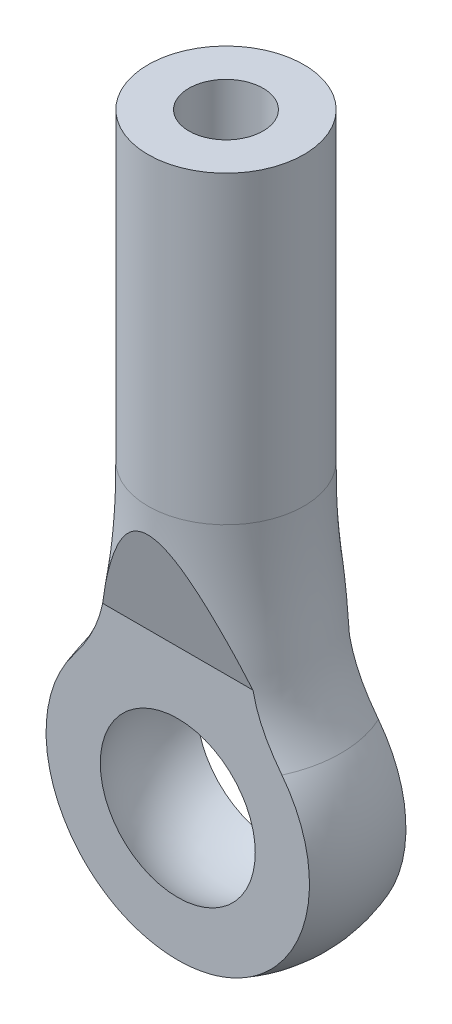
SolidWorks part; units mm, degrees
ref_plane "Front Plane" through (0, 0, 0) normal (0, 0, 1) x (1, 0, 0)
ref_plane "Top Plane" through (0, 0, 0) normal (0, 1, 0) x (1, 0, 0)
ref_plane "Right Plane" through (0, 0, 0) normal (1, 0, 0) x (0, 0, -1)
sketch "Sketch1" plane through (0, 0, 0) normal (0, 0, 1) x (1, 0, 0)
  line L0 (0, 15.65) -> (0, 0) construction
  line L1 (0, 15.65) -> (-2.1, 15.65)
  line L2 (-2.1, 15.65) -> (-2.1, 7.4436)
  line L3 (-2.1, 4.7666) -> (-2.1, 5.7762) construction
  line L4 (-3.3145, 1.8573) -> (-2.8734, 2.4859) construction
  line L5 (-5.6007, -3.78) -> (7.1758, -3.78) construction
  line L6 (0, 0) -> (0, -3.78) construction
  line L7 (0, 15.65) -> (0, -3.78)
  arc A0 (-3.094, 2.1716) -> (0, -3.78) centre (0, 0) ccw
  spline S0 degree 3 poles (-2.1, 7.4436) (-2.1, 6.039) (-2.216, 5.0749) (-2.4052, 3.7427) (-2.507, 3.0078) (-3.094, 2.1716) knots 0 0 0 0 0.498932 0.598932 1 1 1 1
  dimension "D1" = 7.56
  dimension "D2" = 2.1
  dimension "D3" = 19.43
revolve "Revolve1" add sketch "Sketch1" angle 360 about L7
sketch "Sketch2" plane through (0, 0, 0) normal (1, 0, 0) x (0, 0, -1)
  line L0 (-1.3, 3.7649) -> (-1.3, -3.9631)
  line L5 (-6.2868, 4.3665) -> (-6.2868, -3.9631)
  line L6 (-6.2868, -3.9631) -> (-1.3, -3.9631)
  line L7 (0, -4.3231) -> (0, 4.8679) construction
  line L8 (-1.3, 3.7649) -> (-2.8585, 9.5814)
  line L9 (-2.8585, 9.5814) -> (-6.2868, 9.5814)
  line L10 (-6.2868, 9.5814) -> (-6.2868, 4.3665)
  line L11 (1.3, 3.7649) -> (2.8585, 9.5814)
  line L12 (2.8585, 9.5814) -> (6.2868, 9.5814)
  line L13 (6.2868, 9.5814) -> (6.2868, 4.3665)
  line L14 (6.2868, 4.3665) -> (6.2868, -3.9631)
  line L15 (6.2868, -3.9631) -> (1.3, -3.9631)
  line L16 (1.3, 3.7649) -> (1.3, -3.9631)
  dimension "D1" = 1.3
  dimension "D2" = 165
extrude "Cut-Extrude1" cut sketch "Sketch2" against normal blind 10 and the other way blind 10
sketch "Sketch3" plane through (0, 0, 0) normal (0, 0, 1) x (1, 0, 0)
  line L0 (0, -2.46) -> (0, 2.46) construction
  line L1 (0, -2.46) -> (0, 2.46)
  arc A0 (0, 2.46) -> (0, -2.46) centre (0, 0) ccw
  dimension "D1" = 4.92
revolve "Cut-Revolve1" cut sketch "Sketch3" angle 360 about L0
sketch "Sketch4" plane through (0, 15.65, 0) normal (0, 1, 0) x (1, 0, 0)
  circle A0 centre (0, 0) radius 1
extrude "Cut-Extrude2" cut sketch "Sketch4" against normal blind 10
